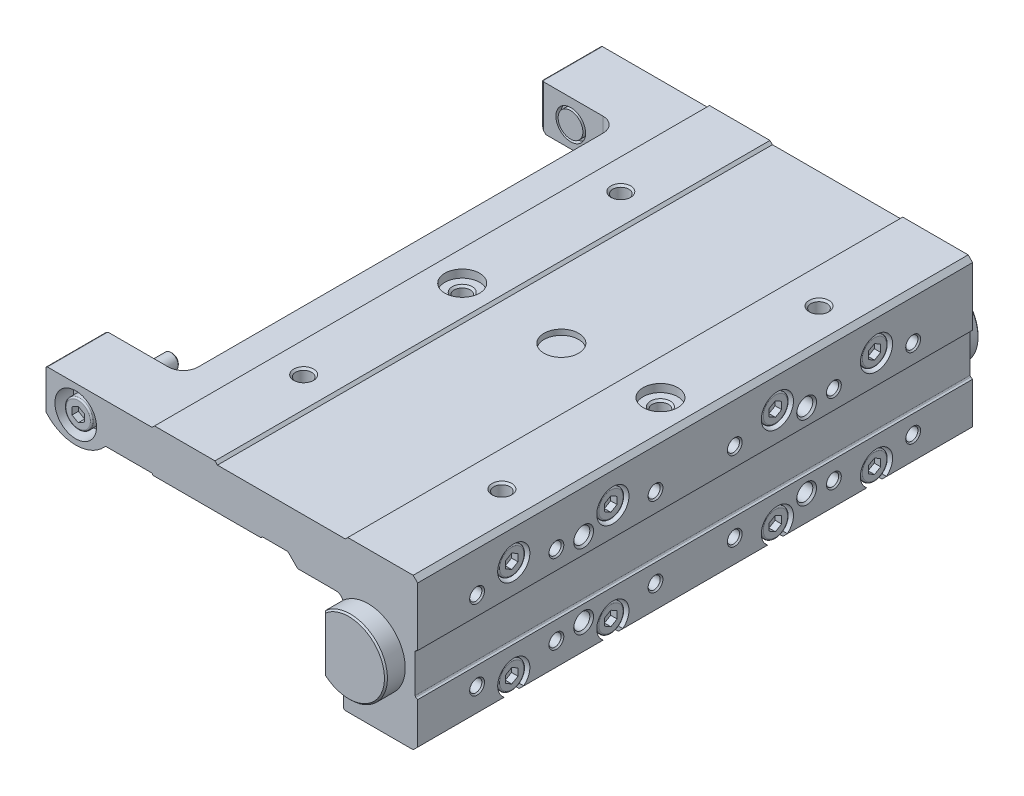
SolidWorks part; units mm, degrees
ref_plane "Front Plane" through (0, 0, 0) normal (0, 0, 1) x (1, 0, 0)
ref_plane "Top Plane" through (0, 0, 0) normal (0, 1, 0) x (1, 0, 0)
ref_plane "Right Plane" through (0, 0, 0) normal (1, 0, 0) x (0, 0, -1)
sketch "Sketch1" plane through (0, 0, 0) normal (0, 0, 1) x (1, 0, 0)
  line L0 (-35.7711, -8.5) -> (-26.7, -8.5)
  line L1 (-26.3127, -8.8) -> (-4.6873, -8.8)
  line L2 (-4.3, -8.5) -> (0.6757, -8.5)
  line L3 (0.8879, -8.5879) -> (2.7414, -10.4414)
  line L4 (2.8828, -10.5) -> (10.5, -10.5)
  line L5 (12, -12) -> (12, -30)
  line L6 (12.5, -30.5) -> (25.9757, -30.5)
  line L7 (26.1879, -30.4121) -> (27, -29.6)
  line L8 (27, -29.6) -> (27, -21.2887)
  line L9 (27, -21.2887) -> (26.65, -21.0866)
  line L10 (26.5, -20.8268) -> (26.5, -13.1732)
  line L11 (26.65, -12.9134) -> (27, -12.7113)
  line L12 (27, -12.7113) -> (27, -0.9)
  line L13 (27, -0.9) -> (26.1, 0)
  line L14 (26.1, 0) -> (12.9, 0)
  line L15 (12.9, 0) -> (12.4, -0.5)
  line L16 (12.4, -0.5) -> (-13.4, -0.5)
  line L17 (-13.4, -0.5) -> (-13.9, 0)
  line L18 (-13.9, 0) -> (-26.1, 0)
  line L19 (-26.1, 0) -> (-26.6, -0.5)
  line L20 (-26.6, -0.5) -> (-47.7, -0.5)
  line L21 (-48, -0.8) -> (-48, -8.3897)
  arc A0 (-48, -8.3897) -> (-47.9271, -8.5857) centre (-47.7, -8.3897) ccw
  arc A1 (-47.9271, -8.5857) -> (-36.145, -8.6681) centre (-42, -3.4706) ccw
  arc A2 (-36.145, -8.6681) -> (-35.7711, -8.5) centre (-35.7711, -9) cw
  arc A3 (-26.7, -8.5) -> (-26.5064, -8.65) centre (-26.7, -8.7) cw
  arc A4 (-26.5064, -8.65) -> (-26.3127, -8.8) centre (-26.3127, -8.6) ccw
  arc A5 (-4.6873, -8.8) -> (-4.4936, -8.65) centre (-4.6873, -8.6) ccw
  arc A6 (-4.4936, -8.65) -> (-4.3, -8.5) centre (-4.3, -8.7) cw
  arc A7 (0.6757, -8.5) -> (0.8879, -8.5879) centre (0.6757, -8.8) cw
  arc A8 (2.7414, -10.4414) -> (2.8828, -10.5) centre (2.8828, -10.3) ccw
  arc A9 (10.5, -10.5) -> (12, -12) centre (10.5, -12) cw
  arc A10 (12, -30) -> (12.5, -30.5) centre (12.5, -30) ccw
  arc A11 (25.9757, -30.5) -> (26.1879, -30.4121) centre (25.9757, -30.2) ccw
  arc A12 (26.65, -21.0866) -> (26.5, -20.8268) centre (26.8, -20.8268) cw
  arc A13 (26.5, -13.1732) -> (26.65, -12.9134) centre (26.8, -13.1732) cw
  arc A14 (-47.7, -0.5) -> (-48, -0.8) centre (-47.7, -0.8) ccw
extrude "Boss-Extrude1" add sketch "Sketch1" against normal blind 56 and the other way blind 56
sketch "Sketch2" plane through (0, 0, 0) normal (0, 1, 0) x (1, 0, 0)
  line L0 (-48, 44.1887) -> (-48, -44.0887)
  line L1 (-48, -44.0887) -> (-47.5, -43.8)
  line L2 (-47.5, -43.8) -> (-35.5, -43.8)
  line L3 (-32.5, -40.8) -> (-32.5, 40.9)
  line L4 (-35.5, 43.9) -> (-47.5, 43.9)
  line L5 (-47.5, 43.9) -> (-48, 44.1887)
  arc A0 (-35.5, -43.8) -> (-32.5, -40.8) centre (-35.5, -40.8) ccw
  arc A1 (-32.5, 40.9) -> (-35.5, 43.9) centre (-35.5, 40.9) ccw
extrude "Cut-Extrude1" cut sketch "Sketch2" against normal blind 17.6
ref_plane "Plane1" through (0, -3.5, 0) normal (0, 1, 0) x (1, 0, 0)
sketch "Sketch3" plane through (0, -3.5, 0) normal (0, 1, 0) x (1, 0, 0)
  line L0 (5, -51.8) -> (13, -51.8)
  line L1 (13, -51.8) -> (13, 51.8)
  line L2 (13, 51.8) -> (5, 51.8)
  line L3 (-3, 43.8) -> (-3, -43.8)
  arc A0 (-3, -43.8) -> (5, -51.8) centre (5, -43.8) ccw
  arc A1 (5, 51.8) -> (-3, 43.8) centre (5, 43.8) ccw
extrude "Cut-Extrude2" cut sketch "Sketch3" against normal blind 32
sketch "Sketch4" plane through (0, 0, 0) normal (0, 0, 1) x (1, 0, 0)
  line L0 (20, 0) -> (23.5, 0)
  line L1 (23.5, 0) -> (23.5, -1.6)
  line L2 (23.5, -1.6) -> (22, -1.6)
  line L3 (22, -1.6) -> (21.621, -1.979)
  line L4 (21.621, -1.979) -> (21.621, -10)
  line L5 (21.621, -10) -> (20, -10.9359)
  line L6 (20, -10.9359) -> (20, 0)
  line L7 (20, -10.9359) -> (20, 0) construction
revolve "Cut-Revolve1" cut sketch "Sketch4" angle 360 about L7 reverse direction yes
cosmetic thread "Cosmetic Thread1" parameters "D1"=8.4, "D2"=4
sketch "Sketch5" plane through (0, 0, 0) normal (0, 0, 1) x (1, 0, 0)
  line L0 (-20, 0) -> (-16.5, 0)
  line L1 (-16.5, 0) -> (-16.5, -1.6)
  line L2 (-16.5, -1.6) -> (-18, -1.6)
  line L3 (-18, -1.6) -> (-18.379, -1.979)
  line L4 (-18.379, -1.979) -> (-18.379, -10)
  line L5 (-18.379, -10) -> (-20, -10.9359)
  line L6 (-20, -10.9359) -> (-20, 0)
  line L7 (-20, -10.9359) -> (-20, 0) construction
revolve "Cut-Revolve2" cut sketch "Sketch5" angle 360 about L7 reverse direction yes
cosmetic thread "Cosmetic Thread2" parameters "D1"=7.2, "D2"=4
sketch "Sketch6" plane through (0, 0, 0) normal (0, 0, 1) x (1, 0, 0)
  line L0 (0, 0) -> (3.5, 0)
  line L1 (3.5, 0) -> (3.5, -1.6)
  line L2 (3.5, -1.6) -> (0, -1.6)
  line L3 (0, -1.6) -> (0, 0)
  line L4 (0, -1.6) -> (0, 0) construction
revolve "Cut-Revolve3" cut sketch "Sketch6" angle 360 about L4 reverse direction yes
ref_plane "Plane2" through (0, 0, 32) normal (0, 0, 1) x (1, 0, 0)
sketch "Sketch7" plane through (0, 0, 32) normal (0, 0, 1) x (1, 0, 0)
  line L0 (20, 0) -> (22, 0)
  line L1 (22, 0) -> (21.621, -0.379)
  line L2 (21.621, -0.379) -> (21.621, -10)
  line L3 (21.621, -10) -> (20, -10.9359)
  line L4 (20, -10.9359) -> (20, 0)
  line L5 (20, -10.9359) -> (20, 0) construction
revolve "Cut-Revolve4" cut sketch "Sketch7" angle 360 about L5 reverse direction yes
cosmetic thread "Cosmetic Thread3" parameters "D1"=10, "D2"=4
sketch "Sketch8" plane through (0, 0, 0) normal (0, 1, 0) x (1, 0, 0)
  line L0 (20, -32) -> (20, 32)
pattern_linear "LPattern1" count 2 spacing 64 along (0, 0, -1) of "Cut-Revolve4"
cosmetic thread "Cosmetic Thread4" parameters "D1"=10, "D2"=4
sketch "Sketch9" plane through (0, 0, 32) normal (0, 0, 1) x (1, 0, 0)
  line L0 (-20, 0) -> (-18, 0)
  line L1 (-18, 0) -> (-18.379, -0.379)
  line L2 (-18.379, -0.379) -> (-18.379, -10)
  line L3 (-18.379, -10) -> (-20, -10.9359)
  line L4 (-20, -10.9359) -> (-20, 0)
  line L5 (-20, -10.9359) -> (-20, 0) construction
revolve "Cut-Revolve5" cut sketch "Sketch9" angle 360 about L5 reverse direction yes
cosmetic thread "Cosmetic Thread5" parameters "D1"=8.8, "D2"=4
sketch "Sketch10" plane through (0, 0, 0) normal (0, 1, 0) x (1, 0, 0)
  line L0 (-20, -32) -> (-20, 32)
pattern_linear "LPattern2" count 2 spacing 64 along (0, 0, -1) of "Cut-Revolve5"
cosmetic thread "Cosmetic Thread6" parameters "D1"=8.8, "D2"=4
ref_plane "Plane3" through (0, -9, 0) normal (0, 1, 0) x (1, 0, 0)
sketch "Sketch11" plane through (0, -9, 0) normal (0, 1, 0) x (1, 0, 0)
  line L0 (19.2901, 44) -> (20, 45.2295)
  line L1 (20, 45.2295) -> (26.7295, 45.2295)
  line L2 (26.7295, 45.2295) -> (27, 45.5)
  line L3 (27, 45.5) -> (27, 44)
  line L4 (27, 44) -> (19.2901, 44)
  line L5 (27, 44) -> (19.2901, 44) construction
revolve "Cut-Revolve6" cut sketch "Sketch11" angle 360 about L5 reverse direction yes
cosmetic thread "Cosmetic Thread7" parameters "D1"=7, "D2"=3
ref_plane "Plane4" through (27, 0, 0) normal (1, 0, 0) x (0, 0, -1)
sketch "Sketch12" plane through (27, 0, 0) normal (1, 0, 0) x (0, 0, -1)
  line L0 (44, -9) -> (-44, -9)
  line L1 (44, -9) -> (44, -25)
pattern_linear "LPattern3" count 23 spacing 4 along (0, 0, 1) count 2 spacing 16 along (0, -1, 0) skipping (1, 0), (1, 1), (2, 0), (2, 1), (3, 0), (3, 1), (5, 0), (5, 1), (6, 0), (6, 1), (7, 0), (7, 1), (8, 0), (8, 1), (10, 0), (10, 1), (11, 0), (11, 1), (12, 0), (12, 1), (14, 0), (14, 1), (15, 0), (15, 1), (16, 0), (16, 1), (17, 0), (17, 1), (19, 0), (19, 1), (20, 0), (20, 1), (21, 0), (21, 1) of "Cut-Revolve6"
cosmetic thread "Cosmetic Thread8" parameters "D1"=7, "D2"=3
cosmetic thread "Cosmetic Thread9" parameters "D1"=7, "D2"=3
cosmetic thread "Cosmetic Thread10" parameters "D1"=7, "D2"=3
cosmetic thread "Cosmetic Thread11" parameters "D1"=7, "D2"=3
cosmetic thread "Cosmetic Thread12" parameters "D1"=7, "D2"=3
cosmetic thread "Cosmetic Thread13" parameters "D1"=7, "D2"=3
cosmetic thread "Cosmetic Thread14" parameters "D1"=7, "D2"=3
cosmetic thread "Cosmetic Thread15" parameters "D1"=7, "D2"=3
cosmetic thread "Cosmetic Thread16" parameters "D1"=7, "D2"=3
cosmetic thread "Cosmetic Thread17" parameters "D1"=7, "D2"=3
cosmetic thread "Cosmetic Thread18" parameters "D1"=7, "D2"=3
cosmetic thread "Cosmetic Thread19" parameters "D1"=7, "D2"=3
cosmetic thread "Cosmetic Thread20" parameters "D1"=7, "D2"=3
cosmetic thread "Cosmetic Thread21" parameters "D1"=7, "D2"=3
cosmetic thread "Cosmetic Thread22" parameters "D1"=7, "D2"=3
cosmetic thread "Cosmetic Thread23" parameters "D1"=7, "D2"=3
cosmetic thread "Cosmetic Thread24" parameters "D1"=7, "D2"=3
cosmetic thread "Cosmetic Thread25" parameters "D1"=7, "D2"=3
cosmetic thread "Cosmetic Thread26" parameters "D1"=7, "D2"=3
cosmetic thread "Cosmetic Thread27" parameters "D1"=7, "D2"=3
cosmetic thread "Cosmetic Thread28" parameters "D1"=7, "D2"=3
cosmetic thread "Cosmetic Thread29" parameters "D1"=7, "D2"=3
cosmetic thread "Cosmetic Thread30" parameters "D1"=7, "D2"=3
cosmetic thread "Cosmetic Thread31" parameters "D1"=7, "D2"=3
cosmetic thread "Cosmetic Thread32" parameters "D1"=7, "D2"=3
cosmetic thread "Cosmetic Thread33" parameters "D1"=7, "D2"=3
cosmetic thread "Cosmetic Thread34" parameters "D1"=7, "D2"=3
cosmetic thread "Cosmetic Thread35" parameters "D1"=7, "D2"=3
cosmetic thread "Cosmetic Thread36" parameters "D1"=7, "D2"=3
cosmetic thread "Cosmetic Thread37" parameters "D1"=7, "D2"=3
cosmetic thread "Cosmetic Thread38" parameters "D1"=7, "D2"=3
cosmetic thread "Cosmetic Thread39" parameters "D1"=7, "D2"=3
cosmetic thread "Cosmetic Thread40" parameters "D1"=7, "D2"=3
cosmetic thread "Cosmetic Thread41" parameters "D1"=7, "D2"=3
cosmetic thread "Cosmetic Thread42" parameters "D1"=7, "D2"=3
cosmetic thread "Cosmetic Thread43" parameters "D1"=7, "D2"=3
cosmetic thread "Cosmetic Thread44" parameters "D1"=7, "D2"=3
cosmetic thread "Cosmetic Thread45" parameters "D1"=7, "D2"=3
cosmetic thread "Cosmetic Thread46" parameters "D1"=7, "D2"=3
cosmetic thread "Cosmetic Thread47" parameters "D1"=7, "D2"=3
cosmetic thread "Cosmetic Thread48" parameters "D1"=7, "D2"=3
cosmetic thread "Cosmetic Thread49" parameters "D1"=7, "D2"=3
cosmetic thread "Cosmetic Thread50" parameters "D1"=7, "D2"=3
cosmetic thread "Cosmetic Thread51" parameters "D1"=7, "D2"=3
cosmetic thread "Cosmetic Thread52" parameters "D1"=7, "D2"=3
ref_plane "Plane5" through (0, -9.5, 0) normal (0, 1, 0) x (1, 0, 0)
sketch "Sketch13" plane through (0, -9.5, 0) normal (0, 1, 0) x (1, 0, 0)
  line L0 (19.0641, 22.5) -> (20, 24.121)
  line L1 (20, 24.121) -> (26.621, 24.121)
  line L2 (26.621, 24.121) -> (27, 24.5)
  line L3 (27, 24.5) -> (27, 22.5)
  line L4 (27, 22.5) -> (19.0641, 22.5)
  line L5 (27, 22.5) -> (19.0641, 22.5) construction
revolve "Cut-Revolve7" cut sketch "Sketch13" angle 360 about L5 reverse direction yes
cosmetic thread "Cosmetic Thread53" parameters "D1"=7, "D2"=4
sketch "Sketch14" plane through (27, 0, 0) normal (1, 0, 0) x (0, 0, -1)
  line L0 (22.5, -9.5) -> (-22.5, -9.5)
  line L1 (22.5, -9.5) -> (22.5, -24.5)
pattern_linear "LPattern4" count 2 spacing 45 along (0, 0, 1) count 2 spacing 15 along (0, -1, 0) of "Cut-Revolve7"
cosmetic thread "Cosmetic Thread54" parameters "D1"=7, "D2"=4
cosmetic thread "Cosmetic Thread55" parameters "D1"=7, "D2"=4
cosmetic thread "Cosmetic Thread56" parameters "D1"=7, "D2"=4
ref_plane "Plane6" through (0, -30.5, 0) normal (0, 1, 0) x (1, 0, 0)
sketch "Sketch15" plane through (0, -30.5, 0) normal (0, 1, 0) x (1, 0, 0)
  line L0 (23.6, -34.8) -> (23.6, -38.4)
  line L1 (23.8, -38.6) -> (40, -38.6)
  line L2 (40, -38.6) -> (40, 38.6)
  line L3 (40, 38.6) -> (23.8, 38.6)
  line L4 (23.6, 38.4) -> (23.6, 34.8)
  line L5 (23.8, 34.6) -> (35, 34.6)
  line L6 (35, 34.6) -> (35, 18.6)
  line L7 (35, 18.6) -> (23.8, 18.6)
  line L8 (23.6, 18.4) -> (23.6, 14.8)
  line L9 (23.8, 14.6) -> (35, 14.6)
  line L10 (35, 14.6) -> (35, -14.6)
  line L11 (35, -14.6) -> (23.8, -14.6)
  line L12 (23.6, -14.8) -> (23.6, -18.4)
  line L13 (23.8, -18.6) -> (35, -18.6)
  line L14 (35, -18.6) -> (35, -34.6)
  line L15 (35, -34.6) -> (23.8, -34.6)
  arc A0 (23.6, -38.4) -> (23.8, -38.6) centre (23.8, -38.4) ccw
  arc A1 (23.8, 38.6) -> (23.6, 38.4) centre (23.8, 38.4) ccw
  arc A2 (23.6, 34.8) -> (23.8, 34.6) centre (23.8, 34.8) ccw
  arc A3 (23.8, 18.6) -> (23.6, 18.4) centre (23.8, 18.4) ccw
  arc A4 (23.6, 14.8) -> (23.8, 14.6) centre (23.8, 14.8) ccw
  arc A5 (23.8, -14.6) -> (23.6, -14.8) centre (23.8, -14.8) ccw
  arc A6 (23.6, -18.4) -> (23.8, -18.6) centre (23.8, -18.4) ccw
  arc A7 (23.8, -34.6) -> (23.6, -34.8) centre (23.8, -34.8) ccw
extrude "Cut-Extrude3" cut sketch "Sketch15" along normal blind 3.25
ref_plane "Plane7" through (0, -7, 0) normal (0, 1, 0) x (1, 0, 0)
sketch "Sketch16" plane through (0, -7, 0) normal (0, 1, 0) x (1, 0, 0)
  line L0 (23.6, 36.6) -> (23.6, 39.65)
  line L1 (23.8, 39.85) -> (27, 39.85)
  line L2 (27, 39.85) -> (27, 36.6)
  line L3 (27, 36.6) -> (23.6, 36.6)
  line L4 (27, 36.6) -> (23.6, 36.6) construction
  arc A0 (23.6, 39.65) -> (23.8, 39.85) centre (23.8, 39.65) cw
revolve "Cut-Revolve8" cut sketch "Sketch16" angle 360 about L4 reverse direction yes
ref_plane "Plane8" through (0, -27, 0) normal (0, 1, 0) x (1, 0, 0)
sketch "Sketch18" plane through (0, -27, 0) normal (0, 1, 0) x (1, 0, 0)
  line L0 (23.6, 36.6) -> (23.6, 39.65)
  line L1 (23.8, 39.85) -> (27, 39.85)
  line L2 (27, 39.85) -> (27, 36.6)
  line L3 (27, 36.6) -> (23.6, 36.6)
  line L4 (27, 36.6) -> (23.6, 36.6) construction
  arc A0 (23.6, 39.65) -> (23.8, 39.85) centre (23.8, 39.65) cw
sketch "Sketch19" plane through (0, -7, 0) normal (0, 1, 0) x (1, 0, 0)
  line L0 (23.6, 16.6) -> (23.6, 19.65)
  line L1 (23.8, 19.85) -> (27, 19.85)
  line L2 (27, 19.85) -> (27, 16.6)
  line L3 (27, 16.6) -> (23.6, 16.6)
  line L4 (27, 16.6) -> (23.6, 16.6) construction
  arc A0 (23.6, 19.65) -> (23.8, 19.85) centre (23.8, 19.65) cw
sketch "Sketch20" plane through (0, -27, 0) normal (0, 1, 0) x (1, 0, 0)
  line L0 (23.6, 16.6) -> (23.6, 19.65)
  line L1 (23.8, 19.85) -> (27, 19.85)
  line L2 (27, 19.85) -> (27, 16.6)
  line L3 (27, 16.6) -> (23.6, 16.6)
  line L4 (27, 16.6) -> (23.6, 16.6) construction
  arc A0 (23.6, 19.65) -> (23.8, 19.85) centre (23.8, 19.65) cw
sketch "Sketch21" plane through (0, -7, 0) normal (0, 1, 0) x (1, 0, 0)
  line L0 (23.6, -16.6) -> (23.6, -13.55)
  line L1 (23.8, -13.35) -> (27, -13.35)
  line L2 (27, -13.35) -> (27, -16.6)
  line L3 (27, -16.6) -> (23.6, -16.6)
  line L4 (27, -16.6) -> (23.6, -16.6) construction
  arc A0 (23.6, -13.55) -> (23.8, -13.35) centre (23.8, -13.55) cw
sketch "Sketch22" plane through (0, -27, 0) normal (0, 1, 0) x (1, 0, 0)
  line L0 (23.6, -16.6) -> (23.6, -13.55)
  line L1 (23.8, -13.35) -> (27, -13.35)
  line L2 (27, -13.35) -> (27, -16.6)
  line L3 (27, -16.6) -> (23.6, -16.6)
  line L4 (27, -16.6) -> (23.6, -16.6) construction
  arc A0 (23.6, -13.55) -> (23.8, -13.35) centre (23.8, -13.55) cw
sketch "Sketch23" plane through (0, -7, 0) normal (0, 1, 0) x (1, 0, 0)
  line L0 (23.6, -36.6) -> (23.6, -33.55)
  line L1 (23.8, -33.35) -> (27, -33.35)
  line L2 (27, -33.35) -> (27, -36.6)
  line L3 (27, -36.6) -> (23.6, -36.6)
  line L4 (27, -36.6) -> (23.6, -36.6) construction
  arc A0 (23.6, -33.55) -> (23.8, -33.35) centre (23.8, -33.55) cw
sketch "Sketch24" plane through (0, -27, 0) normal (0, 1, 0) x (1, 0, 0)
  line L0 (23.6, -36.6) -> (23.6, -33.55)
  line L1 (23.8, -33.35) -> (27, -33.35)
  line L2 (27, -33.35) -> (27, -36.6)
  line L3 (27, -36.6) -> (23.6, -36.6)
  line L4 (27, -36.6) -> (23.6, -36.6) construction
  arc A0 (23.6, -33.55) -> (23.8, -33.35) centre (23.8, -33.55) cw
revolve "Cut-Revolve9" cut sketch "Sketch18" angle 360 about L4 reverse direction yes
revolve "Cut-Revolve10" cut sketch "Sketch19" angle 360 about L4 reverse direction yes
revolve "Cut-Revolve11" cut sketch "Sketch20" angle 360 about L4 reverse direction yes
revolve "Cut-Revolve12" cut sketch "Sketch21" angle 360 about L4 reverse direction yes
revolve "Cut-Revolve13" cut sketch "Sketch22" angle 360 about L4 reverse direction yes
revolve "Cut-Revolve14" cut sketch "Sketch23" angle 360 about L4 reverse direction yes
revolve "Cut-Revolve15" cut sketch "Sketch24" angle 360 about L4 reverse direction yes
ref_plane "Plane9" through (0, -30.5, 0) normal (0, 1, 0) x (1, 0, 0)
sketch "Sketch25" plane through (0, -7, 0) normal (0, 1, 0) x (1, 0, 0)
  line L0 (23.6, 36.6) -> (23.6, 39.35)
  line L1 (23.6, 39.35) -> (26.3, 39.35)
  line L2 (26.6, 39.05) -> (26.6, 36.6)
  line L3 (26.6, 36.6) -> (23.6, 36.6)
  line L4 (27, 36.6) -> (23.6, 36.6) construction
  arc A0 (26.3, 39.35) -> (26.6, 39.05) centre (26.3, 39.05) cw
revolve "Revolve1" add sketch "Sketch25" angle 360 about L4 reverse direction yes
sketch "Sketch27" plane through (0, -27, 0) normal (0, 1, 0) x (1, 0, 0)
  line L0 (23.6, 36.6) -> (23.6, 39.35)
  line L1 (23.6, 39.35) -> (26.3, 39.35)
  line L2 (26.6, 39.05) -> (26.6, 36.6)
  line L3 (26.6, 36.6) -> (23.6, 36.6)
  line L4 (27, 36.6) -> (23.6, 36.6) construction
  arc A0 (26.3, 39.35) -> (26.6, 39.05) centre (26.3, 39.05) cw
sketch "Sketch28" plane through (0, -7, 0) normal (0, 1, 0) x (1, 0, 0)
  line L0 (23.6, 16.6) -> (23.6, 19.35)
  line L1 (23.6, 19.35) -> (26.3, 19.35)
  line L2 (26.6, 19.05) -> (26.6, 16.6)
  line L3 (26.6, 16.6) -> (23.6, 16.6)
  line L4 (27, 16.6) -> (23.6, 16.6) construction
  arc A0 (26.3, 19.35) -> (26.6, 19.05) centre (26.3, 19.05) cw
sketch "Sketch29" plane through (0, -27, 0) normal (0, 1, 0) x (1, 0, 0)
  line L0 (23.6, 16.6) -> (23.6, 19.35)
  line L1 (23.6, 19.35) -> (26.3, 19.35)
  line L2 (26.6, 19.05) -> (26.6, 16.6)
  line L3 (26.6, 16.6) -> (23.6, 16.6)
  line L4 (27, 16.6) -> (23.6, 16.6) construction
  arc A0 (26.3, 19.35) -> (26.6, 19.05) centre (26.3, 19.05) cw
sketch "Sketch30" plane through (0, -7, 0) normal (0, 1, 0) x (1, 0, 0)
  line L0 (23.6, -16.6) -> (23.6, -13.85)
  line L1 (23.6, -13.85) -> (26.3, -13.85)
  line L2 (26.6, -14.15) -> (26.6, -16.6)
  line L3 (26.6, -16.6) -> (23.6, -16.6)
  line L4 (27, -16.6) -> (23.6, -16.6) construction
  arc A0 (26.3, -13.85) -> (26.6, -14.15) centre (26.3, -14.15) cw
sketch "Sketch31" plane through (0, -27, 0) normal (0, 1, 0) x (1, 0, 0)
  line L0 (23.6, -16.6) -> (23.6, -13.85)
  line L1 (23.6, -13.85) -> (26.3, -13.85)
  line L2 (26.6, -14.15) -> (26.6, -16.6)
  line L3 (26.6, -16.6) -> (23.6, -16.6)
  line L4 (27, -16.6) -> (23.6, -16.6) construction
  arc A0 (26.3, -13.85) -> (26.6, -14.15) centre (26.3, -14.15) cw
sketch "Sketch32" plane through (0, -7, 0) normal (0, 1, 0) x (1, 0, 0)
  line L0 (23.6, -36.6) -> (23.6, -33.85)
  line L1 (23.6, -33.85) -> (26.3, -33.85)
  line L2 (26.6, -34.15) -> (26.6, -36.6)
  line L3 (26.6, -36.6) -> (23.6, -36.6)
  line L4 (27, -36.6) -> (23.6, -36.6) construction
  arc A0 (26.3, -33.85) -> (26.6, -34.15) centre (26.3, -34.15) cw
sketch "Sketch33" plane through (0, -27, 0) normal (0, 1, 0) x (1, 0, 0)
  line L0 (23.6, -36.6) -> (23.6, -33.85)
  line L1 (23.6, -33.85) -> (26.3, -33.85)
  line L2 (26.6, -34.15) -> (26.6, -36.6)
  line L3 (26.6, -36.6) -> (23.6, -36.6)
  line L4 (27, -36.6) -> (23.6, -36.6) construction
  arc A0 (26.3, -33.85) -> (26.6, -34.15) centre (26.3, -34.15) cw
revolve "Revolve2" add sketch "Sketch27" angle 360 about L4 reverse direction yes
revolve "Revolve3" add sketch "Sketch28" angle 360 about L4 reverse direction yes
revolve "Revolve4" add sketch "Sketch29" angle 360 about L4 reverse direction yes
revolve "Revolve5" add sketch "Sketch30" angle 360 about L4 reverse direction yes
revolve "Revolve6" add sketch "Sketch31" angle 360 about L4 reverse direction yes
revolve "Revolve7" add sketch "Sketch32" angle 360 about L4 reverse direction yes
revolve "Revolve8" add sketch "Sketch33" angle 360 about L4 reverse direction yes
sketch "Sketch34" plane through (27, 0, 0) normal (1, 0, 0) x (0, 0, -1)
  line L0 (35.35, -7.7217) -> (36.6, -8.4434)
  line L1 (36.6, -8.4434) -> (37.85, -7.7217)
  line L2 (37.85, -7.7217) -> (37.85, -6.2783)
  line L3 (37.85, -6.2783) -> (36.6, -5.5566)
  line L4 (36.6, -5.5566) -> (35.35, -6.2783)
  line L5 (35.35, -6.2783) -> (35.35, -7.7217)
extrude "Cut-Extrude4" cut sketch "Sketch34" against normal blind 1.7
sketch "Sketch36" plane through (27, 0, 0) normal (1, 0, 0) x (0, 0, -1)
  line L0 (35.35, -27.7217) -> (36.6, -28.4434)
  line L1 (36.6, -28.4434) -> (37.85, -27.7217)
  line L2 (37.85, -27.7217) -> (37.85, -26.2783)
  line L3 (37.85, -26.2783) -> (36.6, -25.5566)
  line L4 (36.6, -25.5566) -> (35.35, -26.2783)
  line L5 (35.35, -26.2783) -> (35.35, -27.7217)
sketch "Sketch37" plane through (27, 0, 0) normal (1, 0, 0) x (0, 0, -1)
  line L0 (15.35, -7.7217) -> (16.6, -8.4434)
  line L1 (16.6, -8.4434) -> (17.85, -7.7217)
  line L2 (17.85, -7.7217) -> (17.85, -6.2783)
  line L3 (17.85, -6.2783) -> (16.6, -5.5566)
  line L4 (16.6, -5.5566) -> (15.35, -6.2783)
  line L5 (15.35, -6.2783) -> (15.35, -7.7217)
sketch "Sketch38" plane through (27, 0, 0) normal (1, 0, 0) x (0, 0, -1)
  line L0 (15.35, -27.7217) -> (16.6, -28.4434)
  line L1 (16.6, -28.4434) -> (17.85, -27.7217)
  line L2 (17.85, -27.7217) -> (17.85, -26.2783)
  line L3 (17.85, -26.2783) -> (16.6, -25.5566)
  line L4 (16.6, -25.5566) -> (15.35, -26.2783)
  line L5 (15.35, -26.2783) -> (15.35, -27.7217)
sketch "Sketch39" plane through (27, 0, 0) normal (1, 0, 0) x (0, 0, -1)
  line L0 (-17.85, -7.7217) -> (-16.6, -8.4434)
  line L1 (-16.6, -8.4434) -> (-15.35, -7.7217)
  line L2 (-15.35, -7.7217) -> (-15.35, -6.2783)
  line L3 (-15.35, -6.2783) -> (-16.6, -5.5566)
  line L4 (-16.6, -5.5566) -> (-17.85, -6.2783)
  line L5 (-17.85, -6.2783) -> (-17.85, -7.7217)
sketch "Sketch40" plane through (27, 0, 0) normal (1, 0, 0) x (0, 0, -1)
  line L0 (-17.85, -27.7217) -> (-16.6, -28.4434)
  line L1 (-16.6, -28.4434) -> (-15.35, -27.7217)
  line L2 (-15.35, -27.7217) -> (-15.35, -26.2783)
  line L3 (-15.35, -26.2783) -> (-16.6, -25.5566)
  line L4 (-16.6, -25.5566) -> (-17.85, -26.2783)
  line L5 (-17.85, -26.2783) -> (-17.85, -27.7217)
sketch "Sketch41" plane through (27, 0, 0) normal (1, 0, 0) x (0, 0, -1)
  line L0 (-37.85, -7.7217) -> (-36.6, -8.4434)
  line L1 (-36.6, -8.4434) -> (-35.35, -7.7217)
  line L2 (-35.35, -7.7217) -> (-35.35, -6.2783)
  line L3 (-35.35, -6.2783) -> (-36.6, -5.5566)
  line L4 (-36.6, -5.5566) -> (-37.85, -6.2783)
  line L5 (-37.85, -6.2783) -> (-37.85, -7.7217)
sketch "Sketch42" plane through (27, 0, 0) normal (1, 0, 0) x (0, 0, -1)
  line L0 (-37.85, -27.7217) -> (-36.6, -28.4434)
  line L1 (-36.6, -28.4434) -> (-35.35, -27.7217)
  line L2 (-35.35, -27.7217) -> (-35.35, -26.2783)
  line L3 (-35.35, -26.2783) -> (-36.6, -25.5566)
  line L4 (-36.6, -25.5566) -> (-37.85, -26.2783)
  line L5 (-37.85, -26.2783) -> (-37.85, -27.7217)
extrude "Cut-Extrude5" cut sketch "Sketch36" against normal blind 1.7
extrude "Cut-Extrude6" cut sketch "Sketch37" against normal blind 1.7
extrude "Cut-Extrude7" cut sketch "Sketch38" against normal blind 1.7
extrude "Cut-Extrude8" cut sketch "Sketch39" against normal blind 1.7
extrude "Cut-Extrude9" cut sketch "Sketch40" against normal blind 1.7
extrude "Cut-Extrude10" cut sketch "Sketch41" against normal blind 1.7
extrude "Cut-Extrude11" cut sketch "Sketch42" against normal blind 1.7
ref_plane "Plane10" through (13, 0, 0) normal (1, 0, 0) x (0, 0, -1)
sketch "Sketch43" plane through (13, 0, 0) normal (1, 0, 0) x (0, 0, -1)
  line L0 (2.8, -4.95) -> (2.8, -29.05)
  line L1 (3.3, -29.55) -> (5.8, -29.55)
  line L2 (5.8, -29.55) -> (6.45, -30.2)
  line L3 (6.45, -30.2) -> (9.6, -30.2)
  line L4 (9.6, -30.2) -> (9.6, -30.3)
  line L5 (9.6, -30.3) -> (43.6, -30.3)
  line L6 (43.6, -30.3) -> (43.6, -30.2)
  line L7 (43.6, -30.2) -> (46.75, -30.2)
  line L8 (46.75, -30.2) -> (47.4, -29.55)
  line L9 (47.4, -29.55) -> (49.9, -29.55)
  line L10 (50.4, -29.05) -> (50.4, -4.95)
  line L11 (49.9, -4.45) -> (47.4, -4.45)
  line L12 (47.4, -4.45) -> (46.75, -3.8)
  line L13 (46.75, -3.8) -> (43.6, -3.8)
  line L14 (43.6, -3.8) -> (43.6, -3.7)
  line L15 (43.6, -3.7) -> (9.6, -3.7)
  line L16 (9.6, -3.7) -> (9.6, -3.8)
  line L17 (9.6, -3.8) -> (6.45, -3.8)
  line L18 (6.45, -3.8) -> (5.8, -4.45)
  line L19 (5.8, -4.45) -> (3.3, -4.45)
  arc A0 (2.8, -29.05) -> (3.3, -29.55) centre (3.3, -29.05) ccw
  arc A1 (49.9, -29.55) -> (50.4, -29.05) centre (49.9, -29.05) ccw
  arc A2 (50.4, -4.95) -> (49.9, -4.45) centre (49.9, -4.95) ccw
  arc A3 (3.3, -4.45) -> (2.8, -4.95) centre (3.3, -4.95) ccw
extrude "Boss-Extrude2" add sketch "Sketch43" against normal blind 10.2
sketch "Sketch44" plane through (13, 0, 0) normal (1, 0, 0) x (0, 0, -1)
  line L0 (-49.9, -29.55) -> (-47.4, -29.55)
  line L1 (-47.4, -29.55) -> (-46.75, -30.2)
  line L2 (-46.75, -30.2) -> (-43.6, -30.2)
  line L3 (-43.6, -30.2) -> (-43.6, -30.3)
  line L4 (-43.6, -30.3) -> (-9.6, -30.3)
  line L5 (-9.6, -30.3) -> (-9.6, -30.2)
  line L6 (-9.6, -30.2) -> (-6.45, -30.2)
  line L7 (-6.45, -30.2) -> (-5.8, -29.55)
  line L8 (-5.8, -29.55) -> (-3.3, -29.55)
  line L9 (-2.8, -29.05) -> (-2.8, -4.95)
  line L10 (-3.3, -4.45) -> (-5.8, -4.45)
  line L11 (-5.8, -4.45) -> (-6.45, -3.8)
  line L12 (-6.45, -3.8) -> (-9.6, -3.8)
  line L13 (-9.6, -3.8) -> (-9.6, -3.7)
  line L14 (-9.6, -3.7) -> (-43.6, -3.7)
  line L15 (-43.6, -3.7) -> (-43.6, -3.8)
  line L16 (-43.6, -3.8) -> (-46.75, -3.8)
  line L17 (-46.75, -3.8) -> (-47.4, -4.45)
  line L18 (-47.4, -4.45) -> (-49.9, -4.45)
  line L19 (-50.4, -4.95) -> (-50.4, -29.05)
  arc A0 (-50.4, -29.05) -> (-49.9, -29.55) centre (-49.9, -29.05) ccw
  arc A1 (-3.3, -29.55) -> (-2.8, -29.05) centre (-3.3, -29.05) ccw
  arc A2 (-2.8, -4.95) -> (-3.3, -4.45) centre (-3.3, -4.95) ccw
  arc A3 (-49.9, -4.45) -> (-50.4, -4.95) centre (-49.9, -4.95) ccw
extrude "Boss-Extrude3" add sketch "Sketch44" against normal blind 10.2
sketch "Sketch45" plane through (0, 0, 0) normal (0, 0, 1) x (1, 0, 0)
  line L0 (0, -23) -> (3.95, -23)
  line L1 (6.45, -23) -> (7.2, -23)
  line L2 (7.5, -22.7) -> (7.5, -11.3)
  line L3 (7.2, -11) -> (6.45, -11)
  line L4 (3.95, -11) -> (0, -11)
  line L5 (0, -11) -> (0, -23)
  arc A0 (3.95, -23) -> (6.45, -23) centre (5.2, -23) cw
  arc A1 (7.2, -23) -> (7.5, -22.7) centre (7.2, -22.7) ccw
  arc A2 (7.5, -11.3) -> (7.2, -11) centre (7.2, -11.3) ccw
  arc A3 (6.45, -11) -> (3.95, -11) centre (5.2, -11) cw
extrude "Cut-Extrude12" cut sketch "Sketch45" along normal blind 112 and the other way blind 112
ref_plane "Plane11" through (17, 0, 0) normal (1, 0, 0) x (0, 0, -1)
sketch "Sketch46" plane through (17, 0, 0) normal (1, 0, 0) x (0, 0, -1)
  line L0 (56, -17) -> (56, -9.5)
  line L1 (56, -9.5) -> (59.6, -9.5)
  line L2 (59.6, -9.5) -> (59.9, -9.8)
  line L3 (59.9, -9.8) -> (59.9, -17)
  line L4 (59.9, -17) -> (56, -17)
  line L5 (59.9, -17) -> (56, -17) construction
revolve "Revolve9" add sketch "Sketch46" angle 360 about L5 reverse direction yes
sketch "Sketch47" plane through (17, 0, 0) normal (1, 0, 0) x (0, 0, -1)
  line L0 (-59.9, -17) -> (-59.9, -9.8)
  line L1 (-59.9, -9.8) -> (-59.6, -9.5)
  line L2 (-59.6, -9.5) -> (-56, -9.5)
  line L3 (-56, -9.5) -> (-56, -17)
  line L4 (-56, -17) -> (-59.9, -17)
  line L5 (-56, -17) -> (-59.9, -17) construction
revolve "Revolve10" add sketch "Sketch47" angle 360 about L5 reverse direction yes
sketch "Sketch48" plane through (0, 0, 0) normal (0, 1, 0) x (1, 0, 0)
  line L0 (2, 59.9) -> (2, 56)
  line L1 (2, 56) -> (12, 56)
  line L2 (12, 56) -> (12, 59.6)
  line L3 (12, 59.6) -> (12.3, 59.9)
  line L4 (12.3, 59.9) -> (2, 59.9)
extrude "Cut-Extrude13" cut sketch "Sketch48" against normal blind 32
sketch "Sketch49" plane through (0, 0, 0) normal (0, 1, 0) x (1, 0, 0)
  line L0 (2, -59.9) -> (12.3, -59.9)
  line L1 (12.3, -59.9) -> (12, -59.6)
  line L2 (12, -59.6) -> (12, -56)
  line L3 (12, -56) -> (2, -56)
  line L4 (2, -56) -> (2, -59.9)
extrude "Cut-Extrude14" cut sketch "Sketch49" against normal blind 32
ref_plane "Plane12" through (-42, 0, 0) normal (1, 0, 0) x (0, 0, -1)
sketch "Sketch50" plane through (-42, 0, 0) normal (1, 0, 0) x (0, 0, -1)
  line L0 (55.4, -5.25) -> (55.4, -2.25)
  line L1 (55.4, -2.25) -> (51.5, -2.25)
  line L2 (51.5, -2.25) -> (51.5, -1.75)
  line L3 (51.5, -1.75) -> (56, -1.75)
  line L4 (56, -1.75) -> (56, -5.25)
  line L5 (56, -5.25) -> (55.4, -5.25)
  line L6 (56, -5.25) -> (51.5, -5.25) construction
revolve "Cut-Revolve16" cut sketch "Sketch50" angle 360 about L6 reverse direction yes
ref_plane "Plane13" through (0, 0, -56) normal (0, 0, 1) x (1, 0, 0)
sketch "Sketch51" plane through (0, 0, -56) normal (0, 0, 1) x (1, 0, 0)
  line L0 (-43.5, -6.116) -> (-42, -6.9821)
  line L1 (-42, -6.9821) -> (-40.5, -6.116)
  line L2 (-40.5, -6.116) -> (-40.5, -4.384)
  line L3 (-40.5, -4.384) -> (-42, -3.5179)
  line L4 (-42, -3.5179) -> (-43.5, -4.384)
  line L5 (-43.5, -4.384) -> (-43.5, -6.116)
extrude "Cut-Extrude15" cut sketch "Sketch51" along normal blind 4
sketch "Sketch52" plane through (-42, 0, 0) normal (1, 0, 0) x (0, 0, -1)
  line L0 (-56, -6) -> (-56, -1.8)
  line L1 (-56, -1.8) -> (-52.2, -1.8)
  line L2 (-52, -2) -> (-52.5, -2)
  line L3 (-52.5, -2) -> (-52.5, -6)
  line L4 (-52.5, -6) -> (-56, -6)
  line L5 (-52.5, -6) -> (-56, -6) construction
  arc A0 (-52.2, -1.8) -> (-52, -2) centre (-52.2, -2) cw
revolve "Cut-Revolve17" cut sketch "Sketch52" angle 360 about L5 reverse direction yes
sketch "Sketch53" plane through (-42, 0, 0) normal (1, 0, 0) x (0, 0, -1)
  line L0 (-55.5, -6.2) -> (-55.5, -3.75)
  line L1 (-55.2, -3.45) -> (-52.5, -3.45)
  line L2 (-52.5, -3.45) -> (-52.5, -6.2)
  line L3 (-52.5, -6.2) -> (-55.5, -6.2)
  line L4 (-52.5, -6.2) -> (-56, -6.2) construction
  arc A0 (-55.5, -3.75) -> (-55.2, -3.45) centre (-55.2, -3.75) cw
revolve "Revolve11" add sketch "Sketch53" angle 360 about L4 reverse direction yes
sketch "Sketch54" plane through (-42, 0, 0) normal (1, 0, 0) x (0, 0, -1)
  line L0 (-52, -6) -> (-52, -4)
  line L1 (-52, -4) -> (-36, -4)
  line L2 (-36, -4) -> (-36, -6)
  line L3 (-36, -6) -> (-52, -6)
  line L4 (-36, -6) -> (-52, -6) construction
revolve "Cut-Revolve18" cut sketch "Sketch54" angle 360 about L4 reverse direction yes
ref_plane "Plane14" through (0, 0, 56) normal (0, 0, 1) x (1, 0, 0)
sketch "Sketch55" plane through (0, 0, 56) normal (0, 0, 1) x (1, 0, 0)
  line L0 (-43.25, -6.9217) -> (-42, -7.6434)
  line L1 (-42, -7.6434) -> (-40.75, -6.9217)
  line L2 (-40.75, -6.9217) -> (-40.75, -5.4783)
  line L3 (-40.75, -5.4783) -> (-42, -4.7566)
  line L4 (-42, -4.7566) -> (-43.25, -5.4783)
  line L5 (-43.25, -5.4783) -> (-43.25, -6.9217)
extrude "Cut-Extrude16" cut sketch "Sketch55" against normal blind 1.8
sketch "Sketch56" plane through (-42, 0, 0) normal (1, 0, 0) x (0, 0, -1)
  line L0 (-52.5, -6.2) -> (-52.5, -4.7)
  line L1 (-52.5, -4.7) -> (-36.8065, -4.7)
  line L2 (-36.8065, -4.7) -> (-36.5, -5.0065)
  line L3 (-36.5, -5.0065) -> (-36.5, -6.2)
  line L4 (-36.5, -6.2) -> (-52.5, -6.2)
  line L5 (-36.5, -6.2) -> (-52.5, -6.2) construction
revolve "Revolve12" add sketch "Sketch56" angle 360 about L5 reverse direction yes
cosmetic thread "Cosmetic Thread57" parameters "D1"=14.5, "D2"=2.387
sketch "Sketch57" plane through (-42, 0, 0) normal (1, 0, 0) x (0, 0, -1)
  line L0 (-46.35, -29.5) -> (46.35, -29.5)
  line L1 (46.35, -29.5) -> (46.35, -9.5)
  line L2 (46.35, -9.5) -> (-46.35, -9.5)
  line L3 (-46.35, -9.5) -> (-46.35, -29.5)
extrude "Cut-Extrude17" cut sketch "Sketch57" along normal blind 9 and the other way blind 9
sketch "Sketch58" plane through (-42, 0, 0) normal (1, 0, 0) x (0, 0, -1)
  line L0 (42.9, -5.25) -> (42.9, -2.25)
  line L1 (42.9, -2.25) -> (44.9, -2.25)
  line L2 (44.9, -2.25) -> (44.9, -2.75)
  line L3 (44.9, -2.75) -> (43.9, -2.75)
  line L4 (43.9, -2.75) -> (43.9, -5.25)
  line L5 (43.9, -5.25) -> (42.9, -5.25)
  line L6 (44.9, -5.25) -> (42.9, -5.25) construction
revolve "Cut-Revolve19" cut sketch "Sketch58" angle 360 about L6 reverse direction yes
sketch "Sketch59" plane through (-42, 0, 0) normal (1, 0, 0) x (0, 0, -1)
  line L0 (43.85, -5.25) -> (43.85, -2.75)
  line L1 (43.85, -2.75) -> (44.85, -2.75)
  line L2 (44.85, -2.75) -> (44.85, -5.25)
  line L3 (44.85, -5.25) -> (43.85, -5.25)
  line L4 (44.85, -5.25) -> (43.85, -5.25) construction
revolve "Revolve13" add sketch "Sketch59" angle 360 about L4 reverse direction yes
ref_plane "ANBAU XY" through (0, 0, 0) normal (0, 0, 1) x (1, 0, 0)
ref_plane "ANBAU XZ" through (0, -6.2, 0) normal (0, -1, 0) x (-1, 0, 0)
ref_plane "ANBAU YZ" through (-42, 0, 0) normal (1, 0, 0) x (0, 0, -1)
ref_axis "ANBAU X" through (-80.9, -6.2, 0) along (1, 0, 0)
ref_axis "ANBAU Y" through (-42, -50, 0) along (0, 1, 0)
ref_axis "ANBAU Z" through (-42, -6.2, 80.9) along (0, 0, -1)
sketch3d "ANBAU"
  point P0 (-42, -6.2, 0)
ref_plane "H13 XY" through (27, 0, 0) normal (1, 0, 0) x (0, 0, -1)
ref_plane "H13 XZ" through (0, -9, 0) normal (0, -1, 0) x (-1, 0, 0)
ref_plane "H13 YZ" through (0, 0, 44) normal (0, 0, -1) x (-1, 0, 0)
ref_axis "H13 X" through (27, -9, 80.9) along (0, 0, -1)
ref_axis "H13 Y" through (27, -50, 44) along (0, 1, 0)
ref_axis "H13 Z" through (80.9, -9, 44) along (-1, 0, 0)
sketch3d "H13"
  point P0 (27, -9, 44)
other "Freeze***"
